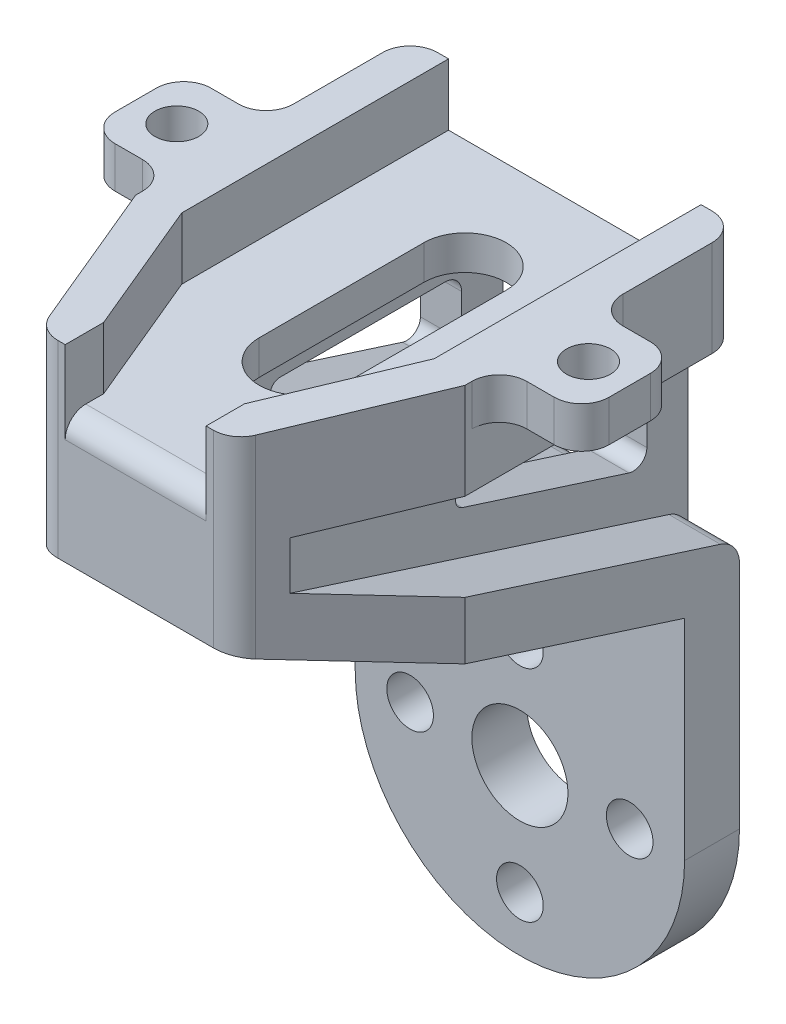
SolidWorks part; units mm, degrees
ref_plane "前视基准面" through (0, 0, 0) normal (0, 0, 1) x (1, 0, 0)
ref_plane "上视基准面" through (0, 0, 0) normal (0, 1, 0) x (1, 0, 0)
ref_plane "右视基准面" through (0, 0, 0) normal (1, 0, 0) x (0, 0, -1)
sketch "草图1" plane through (0, 0, 0) normal (0, 0, 1) x (1, 0, 0)
  line L0 (0, 148.5) -> (0, -94.9538) construction
  line L1 (105, -148.5) -> (-105, -148.5) construction
  line L2 (105, -148.5) -> (105, 148.5) construction
  line L3 (105, 148.5) -> (-105, 148.5) construction
  line L4 (-105, -148.5) -> (-105, 148.5) construction
  line L5 (105, -148.5) -> (-105, 148.5) construction
  line L6 (105, 148.5) -> (-105, -148.5) construction
  line L7 (35.8892, 121.6645) -> (-35.8892, 121.6645)
  line L8 (-35.8892, 121.6645) -> (-66.9017, 102.292)
  line L9 (-75, 40.9339) -> (-75, 31.2613)
  line L10 (-66.9017, 102.292) -> (-66.9017, 52.8701)
  line L11 (75, 40.9339) -> (75, 31.2613)
  line L12 (66.9017, 102.292) -> (66.9017, 52.8701)
  line L13 (35.8892, 121.6645) -> (66.9017, 102.292)
  line L14 (-75, 31.2613) -> (75, 31.2613)
  line L15 (-60, -148.5) -> (-60, -91.8129)
  line L16 (-75, 23.94) -> (75, 23.94)
  line L17 (-75, 23.94) -> (-75, 10.5626)
  line L18 (-38.8455, -105.5906) -> (-66.4608, -113.7617)
  line L19 (-66.4608, -113.7617) -> (-70.1743, -102.7328)
  line L20 (75, 23.94) -> (75, 10.5626)
  line L21 (66.4608, -113.7617) -> (70.1743, -102.7328)
  line L22 (38.8455, -105.5906) -> (66.4608, -113.7617)
  line L23 (-105, 93.0519) -> (105, 93.0519)
  line L24 (-105, 63.0519) -> (105, 63.0519)
  line L25 (-105, -90.0629) -> (-70.5337, -90.0629)
  line L26 (-105, -60.0629) -> (-67.4027, -60.0629)
  line L27 (60, -148.5) -> (60, 148.5)
  line L28 (-60, -58.3129) -> (-45, -58.3129)
  line L29 (-60, -61.8129) -> (-45, -61.8129)
  line L30 (-36, -58.3129) -> (-21, -58.3129)
  line L31 (-36, -61.8129) -> (-21, -61.8129)
  line L32 (-60, -88.3129) -> (-45, -88.3129)
  line L33 (-60, -91.8129) -> (-45, -91.8129)
  line L34 (-36, -88.3129) -> (-21, -88.3129)
  line L35 (-36, -91.8129) -> (-21, -91.8129)
  line L36 (-60, -58.3129) -> (-60, 148.5)
  line L37 (-19.25, -90.0629) -> (105, -90.0629)
  line L38 (-19.25, -60.0629) -> (19.25, -60.0629)
  line L39 (-60, -88.3129) -> (-60, -61.8129)
  line L40 (21, -58.3129) -> (36, -58.3129)
  line L41 (45, -58.3129) -> (60, -58.3129)
  line L42 (60, -61.8129) -> (45, -61.8129)
  line L43 (36, -61.8129) -> (21, -61.8129)
  line L44 (21, -88.3129) -> (36, -88.3129)
  line L45 (21, -91.8129) -> (36, -91.8129)
  line L46 (45, -88.3129) -> (60, -88.3129)
  line L47 (45, -91.8129) -> (60, -91.8129)
  line L48 (37.75, -60.0629) -> (43.25, -60.0629)
  line L49 (58.25, -60.0629) -> (105, -60.0629)
  line L50 (-60, 94.8019) -> (-45, 94.8019)
  line L51 (-36, 94.8019) -> (-21, 94.8019)
  line L52 (-60, 91.3019) -> (-45, 91.3019)
  line L53 (-36, 91.3019) -> (-21, 91.3019)
  line L54 (-60, 64.8019) -> (-45, 64.8019)
  line L55 (-60, 61.3019) -> (-45, 61.3019)
  line L56 (-36, 64.8019) -> (-21, 64.8019)
  line L57 (-36, 61.3019) -> (-21, 61.3019)
  line L58 (21, 94.8019) -> (36, 94.8019)
  line L59 (21, 91.3019) -> (36, 91.3019)
  line L60 (45, 94.8019) -> (60, 94.8019)
  line L61 (45, 91.3019) -> (60, 91.3019)
  line L62 (21, 61.3019) -> (36, 61.3019)
  line L63 (21, 64.8019) -> (36, 64.8019)
  line L64 (45, 61.3019) -> (60, 61.3019)
  line L65 (45, 64.8019) -> (60, 64.8019)
  line L66 (-33.1709, -104.7687) -> (33.1709, -104.7687)
  line L67 (0, -104.7687) -> (0, -148.5) construction
  arc A0 (-75, 40.9339) -> (-66.9017, 52.8701) centre (-79.7474, 52.8701) ccw
  arc A1 (75, 40.9339) -> (66.9017, 52.8701) centre (79.7474, 52.8701) cw
  arc A3 (-60, -88.3129) -> (-60, -91.8129) centre (-60, -90.0629) ccw
  arc A4 (-60, -58.3129) -> (-60, -61.8129) centre (-60, -60.0629) ccw
  circle A5 centre (-60, 63.0519) radius 1.75
  circle A6 centre (-60, 93.0519) radius 1.75
  circle A7 centre (60, 93.0519) radius 1.75
  circle A8 centre (60, 63.0519) radius 1.75
  arc A9 (60, -91.8129) -> (60, -88.3129) centre (60, -90.0629) ccw
  arc A10 (60, -61.8129) -> (60, -58.3129) centre (60, -60.0629) ccw
  arc A11 (-36, -58.3129) -> (-36, -61.8129) centre (-36, -60.0629) ccw
  arc A12 (-36, -88.3129) -> (-36, -91.8129) centre (-36, -90.0629) ccw
  arc A13 (36, -61.8129) -> (36, -58.3129) centre (36, -60.0629) ccw
  arc A14 (36, -91.8129) -> (36, -88.3129) centre (36, -90.0629) ccw
  arc A15 (-45, -61.8129) -> (-45, -58.3129) centre (-45, -60.0629) ccw
  arc A16 (-21, -61.8129) -> (-21, -58.3129) centre (-21, -60.0629) ccw
  arc A17 (-45, -91.8129) -> (-45, -88.3129) centre (-45, -90.0629) ccw
  arc A18 (-21, -91.8129) -> (-21, -88.3129) centre (-21, -90.0629) ccw
  arc A19 (45, -58.3129) -> (45, -61.8129) centre (45, -60.0629) ccw
  arc A20 (21, -58.3129) -> (21, -61.8129) centre (21, -60.0629) ccw
  arc A21 (21, -88.3129) -> (21, -91.8129) centre (21, -90.0629) ccw
  arc A22 (45, -88.3129) -> (45, -91.8129) centre (45, -90.0629) ccw
  circle A23 centre (-36, 93.0519) radius 1.75
  circle A24 centre (-36, 63.0519) radius 1.75
  circle A25 centre (36, 93.0519) radius 1.75
  circle A26 centre (36, 63.0519) radius 1.75
  circle A27 centre (-45, 93.0519) radius 1.75
  circle A28 centre (-21, 93.0519) radius 1.75
  circle A29 centre (-45, 63.0519) radius 1.75
  circle A30 centre (-21, 63.0519) radius 1.75
  circle A31 centre (21, 93.0519) radius 1.75
  circle A32 centre (21, 63.0519) radius 1.75
  circle A33 centre (45, 93.0519) radius 1.75
  circle A34 centre (45, 63.0519) radius 1.75
  arc A35 (33.1709, -104.7687) -> (38.8455, -105.5906) centre (33.1709, -124.7687) cw
  arc A36 (-33.1709, -104.7687) -> (-38.8455, -105.5906) centre (-33.1709, -124.7687) ccw
  spline S0 degree 3 poles (-75, 10.5626) (-72.6959, 1.9073) (-70.3396, -13.3728) (-67.1028, -43.6255) (-66.7657, -72.9327) (-71.8903, -95.1489) (-70.1743, -102.7328) knots 0 0 0 0 0.235247 0.406294 0.801186 1 1 1 1
  spline S1 degree 3 poles (75, 10.5626) (72.6959, 1.9073) (70.3396, -13.3728) (67.1028, -43.6255) (66.7657, -72.9327) (71.8903, -95.1489) (70.1743, -102.7328) knots 0 0 0 0 0.235247 0.406294 0.801186 1 1 1 1
  point P0 (0, 0)
  point P27 (0, 121.6645)
  point P42 (0, -94.0966)
  dimension "D1" = 60
  dimension "D4" = 20
  dimension "D5" = 24
  dimension "D7" = 24
  dimension "D9" = 15
  dimension "D10" = 15
  dimension "D13" = 24
  dimension "D17" = 15
  dimension "D2" = 30
  dimension "D3" = 30
  dimension "D6" = 24
  dimension "D8" = 24
  dimension "D11" = 15
  dimension "D12" = 15
  dimension "D14" = 24
  dimension "D15" = 24
  dimension "D16" = 24
  dimension "D18" = 15
  dimension "D19" = 15
  dimension "D20" = 15
  dimension "D21" = 15
  dimension "D22" = 15
  dimension "D23" = 15
  dimension "D24" = 15
  dimension "D25" = 15
  dimension "D26" = 15
  dimension "D27" = 15
  dimension "D28" = 15
  dimension "D29" = 3.5
  dimension "D30" = 3.5
  dimension "D31" = 3.5
extrude "凸台-拉伸1" add sketch "草图1" along normal blind 3 contours A34 L24 A26 L62 A32 A30 L57 A24 A29 L55 L36 L14 L27 L64 | A5 L24 L10 A0 L9 L14 L36 | A6 L23 L10 L24 A5 L36 | A6 L36 L8 L10 L23 | A33 L60 L27 L13 L7 L8 L36 L50 A27 L23 A23 L51 A28 A31 L58 A25 | A34 L65 L27 L61 A33 L23 A25 L59 A31 A28 L53 A23 A27 L52 L36 L54 A29 L24 A24 L56 A30 A32 L63 A26 | A7 L23 L12 L13 L27 | A8 L24 L12 L23 A7 L27 | A8 L27 L14 L11 A1 L12 L24 | A22 L46 L27 L42 A19 A13 L43 A20 A16 L31 A11 L30 L40 L41 L16 L36 L28 A15 L29 L39 L32 A17 L33 L15 L18 L22 L47 A14 L45 A21 A18 L35 A12 L34 | L17 S0 L19 L18 L15 A3 L39 A4 L36 L16 | S1 L20 L16 L27 A10 L49 | S1 L49 A10 L27 A9 L37 | S1 L37 A9 L27 L22 L21 region at (0, 106.7597, 0) region at (63.3118, 98.9762, 0) region at (-63.3118, 98.9762, 0) region at (63.5153, 78.0519, 0) region at (-63.5153, 78.0519, 0) region at (65.7633, 44.067, 0) region at (0, 78.0519, 0) region at (-65.7633, 44.067, 0) region at (0, 46.6707, 0) region at (0, -40.0712, 0) region at (65.6849, -11.6712, 0) region at (-65.3451, -38.0027, 0) region at (64.4303, -76.0355, 0) region at (65.0264, -100.7629, 0)
sketch "草图7" plane through (0, 0, 0) normal (0, 0, -1) x (-1, 0, 0)
  line L0 (0, 121.6645) -> (0, -104.7687) construction
  line L1 (-35.8892, 121.6645) -> (35.8892, 121.6645) construction
  line L2 (33.1709, -104.7687) -> (-33.1709, -104.7687) construction
  line L3 (0, 41.2613) -> (-21, 41.2613) construction
  line L4 (0, 41.2613) -> (21, 41.2613) construction
  line L5 (0, 13.94) -> (-21, 13.94) construction
  line L6 (0, 13.94) -> (21, 13.94) construction
  line L7 (75, 23.94) -> (-75, 23.94) construction
  line L8 (75, 31.2613) -> (-75, 31.2613) construction
  circle A0 centre (-21, 41.2613) radius 1.75
  circle A1 centre (21, 41.2613) radius 1.75
  circle A2 centre (-21, 13.94) radius 2.25
  circle A3 centre (21, 13.94) radius 2.25
  dimension "D1" = 10
  dimension "D2" = 10
extrude "切除-拉伸2" cut sketch "草图7" against normal through all
sketch "草图9" plane through (0, 0, 3) normal (0, 0, 1) x (1, 0, 0)
  line L0 (-70.7828, -98.747) -> (70.7828, -98.747) construction
  line L1 (0, -98.747) -> (0, -104.7687) construction
  line L2 (55, -100.497) -> (20, -100.497)
  line L3 (-55, -96.997) -> (-20, -96.997)
  line L4 (-55, -100.497) -> (-20, -100.497)
  line L5 (-33.1709, -104.7687) -> (33.1709, -104.7687) construction
  line L6 (55, -96.997) -> (20, -96.997)
  arc A0 (-55, -96.997) -> (-55, -100.497) centre (-55, -98.747) ccw
  arc A1 (-20, -100.497) -> (-20, -96.997) centre (-20, -98.747) ccw
  arc A2 (20, -100.497) -> (20, -96.997) centre (20, -98.747) cw
  arc A3 (55, -96.997) -> (55, -100.497) centre (55, -98.747) cw
  spline S0 degree 3 poles (-75, 10.5626) (-72.6959, 1.9073) (-70.3396, -13.3728) (-67.1028, -43.6255) (-66.7657, -72.9327) (-71.8903, -95.1489) (-70.1743, -102.7328) knots 0 0 0 0 0.235247 0.406294 0.801186 1 1 1 1 construction
  spline S1 degree 3 poles (75, 10.5626) (72.6959, 1.9073) (70.3396, -13.3728) (67.1028, -43.6255) (66.7657, -72.9327) (71.8903, -95.1489) (70.1743, -102.7328) knots 0 0 0 0 0.235247 0.406294 0.801186 1 1 1 1 construction
  dimension "D1" = 35
  dimension "D2" = 20
extrude "切除-拉伸4" cut sketch "草图9" against normal blind 3
sketch "草图10" plane through (0, 0, 3) normal (0, 0, 1) x (1, 0, 0)
  line L0 (-21, -60.0629) -> (-21, -90.0629) construction
  line L1 (21, -60.0629) -> (21, -90.0629) construction
  line L2 (-21, -75.0629) -> (-17.5, -75.0629) construction
  line L4 (12.5, -80.0629) -> (-12.5, -80.0629)
  line L6 (12.5, -70.0629) -> (-12.5, -70.0629)
  line L11 (17.5, -75.0629) -> (21, -75.0629) construction
  arc A0 (-12.5, -70.0629) -> (-12.5, -80.0629) centre (-12.5, -75.0629) ccw
  arc A1 (12.5, -80.0629) -> (12.5, -70.0629) centre (12.5, -75.0629) ccw
  point P11 (0, -75.0629)
extrude "切除-拉伸5" cut sketch "草图10" against normal blind 3
sketch "草图11" plane through (0, 0, 3) normal (0, 0, 1) x (1, 0, 0)
  line L0 (-21, 93.0519) -> (-21, 63.0519) construction
  line L1 (21, 93.0519) -> (21, 63.0519) construction
  line L2 (-21, 78.0519) -> (-20, 78.0519) construction
  line L4 (15, 73.0519) -> (-15, 73.0519)
  line L6 (15, 83.0519) -> (-15, 83.0519)
  line L10 (20, 78.0519) -> (21, 78.0519) construction
  arc A0 (-15, 83.0519) -> (-15, 73.0519) centre (-15, 78.0519) ccw
  arc A1 (15, 73.0519) -> (15, 83.0519) centre (15, 78.0519) ccw
  point P10 (0, 78.0519)
  dimension "D1" = 30
extrude "切除-拉伸8" cut sketch "草图11" against normal blind 3
sketch "草图12" plane through (0, 0, 3) normal (0, 0, 1) x (1, 0, 0)
  line L0 (0, 121.6645) -> (0, 83.0519) construction
  line L1 (35.8892, 121.6645) -> (-35.8892, 121.6645) construction
  line L2 (15, 83.0519) -> (-15, 83.0519) construction
  circle A0 centre (0, 106.3718) radius 11 construction
  circle A1 centre (0, 106.3718) radius 8 construction
  circle A2 centre (0, 114.3718) radius 1.7
  circle A3 centre (0, 98.3718) radius 1.7
  circle A4 centre (8, 106.3718) radius 1.7
  circle A5 centre (-8, 106.3718) radius 1.7
extrude "切除-拉伸9" cut sketch "草图12" against normal blind 3
sketch "草图13" plane through (0, 0, 3) normal (0, 0, 1) x (1, 0, 0)
  line L0 (0, -104.7687) -> (0, -80.0629) construction
  line L1 (-33.1709, -104.7687) -> (33.1709, -104.7687) construction
  line L2 (-12.5, -80.0629) -> (12.5, -80.0629) construction
  circle A0 centre (0, -92.4158) radius 8 construction
  circle A1 centre (0, -84.4158) radius 1.7
  circle A2 centre (8, -92.4158) radius 1.7
  circle A3 centre (0, -100.4158) radius 1.7
  circle A4 centre (-8, -92.4158) radius 1.7
extrude "切除-拉伸11" cut sketch "草图13" against normal blind 3
sketch "草图14" plane through (0, 0, 3) normal (0, 0, 1) x (1, 0, 0)
  line L0 (0, 23.94) -> (0, -104.7687) construction
  line L1 (-55.4755, 8.9197) -> (-55.4755, -46.0803)
  line L2 (-58.9755, 8.9197) -> (-58.9755, -46.0803)
  line L3 (-75, 23.94) -> (75, 23.94) construction
  line L4 (-33.1709, -104.7687) -> (33.1709, -104.7687) construction
  line L5 (58.9755, 8.9197) -> (58.9755, -46.0803)
  line L6 (55.4755, 8.9197) -> (55.4755, -46.0803)
  arc A0 (-55.4755, 8.9197) -> (-58.9755, 8.9197) centre (-57.2255, 8.9197) ccw
  arc A1 (-58.9755, -46.0803) -> (-55.4755, -46.0803) centre (-57.2255, -46.0803) ccw
  arc A2 (58.9755, -46.0803) -> (55.4755, -46.0803) centre (57.2255, -46.0803) cw
  arc A3 (55.4755, 8.9197) -> (58.9755, 8.9197) centre (57.2255, 8.9197) cw
extrude "切除-拉伸12" cut sketch "草图14" against normal through all
fillet "圆角1" radius 2 2 edges at (75, 31.2613, 1.5) (-75, 31.2613, 1.5)
fillet "圆角2" radius 2 2 edges at (-75, 23.94, 1.5) (75, 23.94, 1.5)
sketch "草图15" plane through (0, 0, 0) normal (0, 0, -1) x (-1, 0, 0)
  line L0 (0, 121.6645) -> (0, 31.2613) construction
  line L1 (-35.8892, 121.6645) -> (35.8892, 121.6645) construction
  line L2 (73, 31.2613) -> (-73, 31.2613) construction
  line L3 (-27.5188, 121.6645) -> (-63.6963, 99.0657) construction
  line L4 (-35.8892, 121.6645) -> (-66.9017, 102.292) construction
  line L5 (-61.1842, 102.4035) -> (-34.7748, 118.9006)
  line L6 (-59.5948, 99.8591) -> (-33.1854, 116.3562)
  line L7 (27.5188, 121.6645) -> (63.6963, 99.0657) construction
  line L8 (59.5948, 99.8591) -> (33.1854, 116.3562)
  line L9 (61.1842, 102.4035) -> (34.7748, 118.9006)
  arc A0 (-61.1842, 102.4035) -> (-59.5948, 99.8591) centre (-60.3895, 101.1313) ccw
  arc A1 (-33.1854, 116.3562) -> (-34.7748, 118.9006) centre (-33.9801, 117.6284) ccw
  arc A2 (33.1854, 116.3562) -> (34.7748, 118.9006) centre (33.9801, 117.6284) cw
  arc A3 (61.1842, 102.4035) -> (59.5948, 99.8591) centre (60.3895, 101.1313) cw
extrude "切除-拉伸13" cut sketch "草图15" against normal through all
sketch "草图16" plane through (0, 0, 0) normal (0, 0, -1) x (-1, 0, 0)
  line L0 (0, 121.6645) -> (0, 31.2613) construction
  line L1 (-35.8892, 121.6645) -> (35.8892, 121.6645) construction
  line L2 (73, 31.2613) -> (-73, 31.2613) construction
  line L3 (-21, 41.2613) -> (-66.71, 41.2613) construction
  line L4 (-62, 43.0113) -> (-32, 43.0113)
  line L5 (-62, 39.5113) -> (-32, 39.5113)
  line L6 (21, 41.2613) -> (66.71, 41.2613) construction
  line L7 (62, 39.5113) -> (32, 39.5113)
  line L8 (62, 43.0113) -> (32, 43.0113)
  line L9 (-75, 40.9339) -> (-75, 33.2613) construction
  arc A0 (-62, 43.0113) -> (-62, 39.5113) centre (-62, 41.2613) ccw
  arc A1 (-32, 39.5113) -> (-32, 43.0113) centre (-32, 41.2613) ccw
  arc A2 (32, 39.5113) -> (32, 43.0113) centre (32, 41.2613) cw
  arc A3 (62, 43.0113) -> (62, 39.5113) centre (62, 41.2613) cw
  dimension "D2" = 13
sketch "草图17" plane through (0, 0, 0) normal (0, 0, -1) x (-1, 0, 0)
  text T0 "Y" font "黑体" height in points 72
extrude "切除-拉伸15" cut sketch "草图17" against normal through all
sketch "草图18" plane through (0, 0, 0) normal (0, 0, -1) x (-1, 0, 0)
  text T0 "H" font "黑体" height in points 72
extrude "切除-拉伸16" cut sketch "草图18" against normal through all
sketch "草图20" plane through (0, 0, 0) normal (0, 0, -1) x (-1, 0, 0)
  line L0 (-66.9017, 102.292) -> (-66.9017, 52.8701) construction
  line L1 (-66.9017, 95.8596) -> (66.9017, 95.8596)
  line L2 (-66.9017, 95.8596) -> (-66.9017, 52.8701)
  line L3 (-66.9017, 52.8701) -> (66.9017, 52.8701)
  line L4 (66.9017, 95.8596) -> (66.9017, 52.8701)
extrude "凸台-拉伸2" add sketch "草图20" against normal blind 3
sketch "草图21" plane through (0, 0, 0) normal (0, 0, -1) x (-1, 0, 0)
  line L1 (-64.7663, -56.4228) -> (64.4409, -56.4228)
  line L2 (-64.7663, -56.4228) -> (-64.7663, -95.2117)
  line L3 (-64.7663, -95.2117) -> (64.4409, -95.2117)
  line L4 (64.4409, -56.4228) -> (64.4409, -95.2117)
extrude "凸台-拉伸3" add sketch "草图21" against normal blind 3
sketch "草图22" plane through (0, 0, 0) normal (0, 0, -1) x (-1, 0, 0)
  line L1 (-46.7188, -3.1128) -> (-25.8503, -3.1128)
  line L2 (-46.7188, -3.1128) -> (-46.7188, -34.3233)
  line L3 (-46.7188, -34.3233) -> (-25.8503, -34.3233)
  line L4 (-25.8503, -3.1128) -> (-25.8503, -34.3233)
  line L5 (28.8143, -3.1128) -> (49.8675, -3.1128)
  line L6 (28.8143, -3.1128) -> (28.8143, -33.2152)
  line L7 (28.8143, -33.2152) -> (49.8675, -33.2152)
  line L8 (49.8675, -3.1128) -> (49.8675, -33.2152)
extrude "凸台-拉伸4" add sketch "草图22" against normal blind 3
sketch "草图24" plane through (0, 0, 0) normal (0, 0, -1) x (-1, 0, 0)
  line L1 (-64.9961, 44.3276) -> (-28.6954, 44.3276)
  line L2 (-64.9961, 44.3276) -> (-64.9961, 38.3743)
  line L3 (-64.9961, 38.3743) -> (-28.6954, 38.3743)
  line L4 (-28.6954, 44.3276) -> (-28.6954, 38.3743)
  line L5 (29.2405, 44.3276) -> (65.8315, 44.3276)
  line L6 (29.2405, 44.3276) -> (29.2405, 38.3743)
  line L7 (29.2405, 38.3743) -> (65.8315, 38.3743)
  line L8 (65.8315, 44.3276) -> (65.8315, 38.3743)
extrude "凸台-拉伸5" add sketch "草图24" against normal blind 3
sketch "草图25" plane through (0, 0, 0) normal (0, 0, -1) x (-1, 0, 0)
  line L0 (-32.6582, 113.0113) -> (-14.6582, 113.0113)
  line L1 (-32.6582, 109.5113) -> (-14.6582, 109.5113)
  line L2 (-21, 41.2613) -> (21, 41.2613)
  line L3 (-0.3165, 111.2613) -> (0, 41.2613) construction
  line L4 (14.3418, 113.0113) -> (32.3418, 113.0113)
  line L5 (32.3418, 41.2613) -> (-32.6582, 41.2613)
  line L6 (32.3418, 41.2613) -> (32.3418, 111.2613)
  line L8 (-32.6582, 41.2613) -> (-32.6582, 111.2613)
  line L9 (32.3418, 41.2613) -> (-32.6582, 111.2613) construction
  line L10 (30.7168, 109.5113) -> (-32.6582, 41.2613) construction
  line L11 (14.3418, 109.5113) -> (32.3418, 109.5113)
  line L12 (32.3418, 76.2613) -> (-32.6582, 76.2613) construction
  line L13 (12.5918, 111.2613) -> (-12.9082, 111.2613)
  line L14 (12.5918, 41.2613) -> (-12.9082, 41.2613)
  line L15 (14.3418, 43.0113) -> (32.3418, 43.0113)
  line L16 (14.3418, 39.5113) -> (32.3418, 39.5113)
  line L17 (-32.6582, 43.0113) -> (-14.6582, 43.0113)
  line L18 (-32.6582, 39.5113) -> (-14.6582, 39.5113)
  circle A0 centre (-32.6582, 111.2613) radius 1.75
  arc A1 (32.3418, 109.5113) -> (32.3418, 113.0113) centre (32.3418, 111.2613) ccw
  arc A2 (-14.6582, 109.5113) -> (-14.6582, 113.0113) centre (-14.6582, 111.2613) ccw
  arc A3 (14.3418, 113.0113) -> (14.3418, 109.5113) centre (14.3418, 111.2613) ccw
  arc A4 (14.3418, 39.5113) -> (14.3418, 43.0113) centre (14.3418, 41.2613) cw
  arc A5 (-14.6582, 43.0113) -> (-14.6582, 39.5113) centre (-14.6582, 41.2613) cw
  arc A6 (32.3418, 43.0113) -> (32.3418, 39.5113) centre (32.3418, 41.2613) cw
  circle A7 centre (-32.6582, 41.2613) radius 1.75
  point P9 (-0.1582, 76.2613)
  circle M6 centre (-21, 41.2613) radius 1.75
  circle M7 centre (21, 41.2613) radius 1.75
  dimension "D1" = 18
  dimension "D2" = 18
extrude "切除-拉伸17" cut sketch "草图25" against normal through all contours A0 | A2 L0 A0 L1 | L4 A3 L11 A1 | A7 L8 L5 | A7 L5 L8 | L17 A7 L5 M6 | L5 A7 L18 M6 | A5 L17 L2 M6 | A5 L2 L18 M6 | L17 L5 L2 M6 | L18 L2 L5 M6 | A4 L2 L15 M7 | A4 L16 L2 M7 | L16 L5 L2 M7 | L15 L2 L5 M7 | L15 L5 L6 M7 | A6 L6 L5 L16 M7 region at (22.2838, 111.2613, 0) region at (31.4558, 112.4638, 0) region at (31.9155, 42.0041, 0) region at (26.8291, 42.1772, 0) region at (32.9058, 41.0138, 0) region at (-23.3418, 111.2613, 0) region at (16.4547, 42.1363, 0) region at (21, 42.0041, 0) region at (26.8291, 40.3455, 0) region at (21, 40.5186, 0) region at (16.4547, 40.3863, 0) region at (-28.59, 40.5612, 0) region at (-27.3505, 42.1546, 0) region at (-16.2964, 42.1363, 0) region at (-16.2964, 40.3863, 0) region at (-21, 42.0041, 0) region at (-21, 40.5186, 0)
extrude "切除-拉伸19" cut sketch "草图16" against normal through all
sketch "草图26" plane through (0, 0, 0) normal (0, 0, -1) x (-1, 0, 0)
  line L0 (0, 121.6645) -> (0, -104.7687) construction
  line L1 (-35.8892, 121.6645) -> (35.8892, 121.6645) construction
  line L2 (33.1709, -104.7687) -> (-33.1709, -104.7687) construction
  line L4 (15, 71.877) -> (-15, 71.877)
  line L6 (15, 81.877) -> (-15, 81.877)
  arc A0 (-15, 81.877) -> (-15, 71.877) centre (-15, 76.877) ccw
  arc A1 (15, 71.877) -> (15, 81.877) centre (15, 76.877) ccw
  point P6 (0, 76.877)
extrude "切除-拉伸20" cut sketch "草图26" against normal through all
sketch "草图27" plane through (0, 0, 0) normal (0, 0, -1) x (-1, 0, 0)
  line L0 (0, 23.94) -> (0, -104.7687) construction
  line L1 (73, 23.94) -> (-73, 23.94) construction
  line L2 (33.1709, -104.7687) -> (-33.1709, -104.7687) construction
  line L3 (-42.5, -15.81) -> (-10, -15.81)
  line L4 (42.5, -17.56) -> (-42.5, -17.56)
  line L5 (42.5, -17.56) -> (42.5, 5.44)
  line L6 (42.5, 5.44) -> (-42.5, 5.44)
  line L7 (-42.5, -17.56) -> (-42.5, 5.44)
  line L8 (42.5, -17.56) -> (-42.5, 5.44) construction
  line L9 (42.5, 5.44) -> (-42.5, -17.56) construction
  line L10 (-42.5, -19.31) -> (-10, -19.31)
  line L11 (-42.5, 7.19) -> (-10, 7.19)
  line L12 (-42.5, 3.69) -> (-10, 3.69)
  line L13 (10, 7.19) -> (42.5, 7.19)
  line L14 (10, 3.69) -> (42.5, 3.69)
  line L15 (10, -15.81) -> (42.5, -15.81)
  line L16 (10, -19.31) -> (42.5, -19.31)
  circle A0 centre (-42.5, 5.44) radius 1.75
  circle A1 centre (-42.5, -17.56) radius 1.75
  circle A2 centre (42.5, 5.44) radius 1.75
  circle A3 centre (42.5, -17.56) radius 1.75
  circle A4 centre (-10, 5.44) radius 1.75
  circle A5 centre (-10, -17.56) radius 1.75
  circle A6 centre (10, -17.56) radius 1.75
  circle A7 centre (10, 5.44) radius 1.75
  point P6 (0, -6.06)
  dimension "D4" = 10
  dimension "D5" = 10
  dimension "D1" = 30
  dimension "D2" = 85
  dimension "D3" = 23
extrude "切除-拉伸21" cut sketch "草图27" against normal through all contours L6 A0 L7 | L7 A0 L6 | A4 L11 A0 L6 | A4 L6 A0 L12 | L6 A4 | L6 A4 | A7 L6 | A7 L6 | L6 A7 L14 A2 | L13 A7 L6 A2 | A2 L6 L5 | L6 A2 L5 | L7 A1 L4 | L4 A1 L7 | A5 L3 A1 L4 | A5 L4 A1 L10 | L4 A5 | L4 A5 | A6 L4 | A6 L4 | L4 A6 L16 A3 | L15 A6 L4 A3 | L4 A3 L5 | L5 A3 L4 region at (41.7573, -16.8172, 0) region at (26.25, -16.6727, 0) region at (42.7476, -17.8075, 0) region at (10, -16.8172, 0) region at (42.7476, 5.6876, 0) region at (26.25, 4.5528, 0) region at (41.7573, 4.6973, 0) region at (26.25, -18.4472, 0) region at (10, -18.3027, 0) region at (10, 4.6973, 0) region at (26.25, 6.3273, 0) region at (-10, -16.8172, 0) region at (-10, -18.3027, 0) region at (10, 6.1828, 0) region at (-26.25, -16.6727, 0) region at (-26.25, -18.4472, 0) region at (-10, 6.1828, 0) region at (-10, 4.6973, 0) region at (-41.7573, -16.8172, 0) region at (-42.7476, -17.8075, 0) region at (-26.25, 6.3273, 0) region at (-26.25, 4.5528, 0) region at (-41.7573, 4.6973, 0) region at (-42.7476, 5.6876, 0)
sketch "草图28" plane through (0, 0, 0) normal (0, 0, -1) x (-1, 0, 0)
  line L0 (0, 23.94) -> (0, -104.7687) construction
  line L1 (73, 23.94) -> (-73, 23.94) construction
  line L2 (33.1709, -104.7687) -> (-33.1709, -104.7687) construction
  arc A0 (0, -48.8123) -> (-10.2848, -54.2659) centre (-5.1424, -51.5391) ccw
  arc A1 (-10.2848, -54.2659) -> (0, -63.7557) centre (7.9187, -44.8556) ccw
  arc A2 (10.2848, -54.2659) -> (0, -63.7557) centre (-7.9187, -44.8556) cw
  arc A3 (0, -48.8123) -> (10.2848, -54.2659) centre (5.1424, -51.5391) cw
extrude "切除-拉伸22" cut sketch "草图28" against normal through all
sketch "草图29" plane through (0, 0, 0) normal (0, 0, -1) x (-1, 0, 0)
  line L0 (0, 23.94) -> (0, -104.7687) construction
  line L1 (73, 23.94) -> (-73, 23.94) construction
  line L2 (33.1709, -104.7687) -> (-33.1709, -104.7687) construction
  arc A0 (-21.3687, -73.4908) -> (21.3687, -73.4908) centre (0, -58.7579) ccw
  arc A1 (-24.1996, -75.4426) -> (24.1996, -75.4426) centre (0, -58.7579) ccw
  arc A2 (-21.3687, -73.4908) -> (-24.1996, -75.4426) centre (-22.7842, -74.4667) ccw
  arc A3 (24.1996, -75.4426) -> (21.3687, -73.4908) centre (22.7842, -74.4667) ccw
extrude "切除-拉伸23" cut sketch "草图29" against normal blind 3
ref_plane "基准面1" through (0, 0, -10) normal (0, 0, -1) x (-1, 0, 0)
sketch "草图30" plane through (0, 0, -10) normal (0, 0, -1) x (-1, 0, 0)
  line L0 (-8, 106.3718) -> (8, 106.3718) construction
  line L1 (-12, 106.3718) -> (-12, 141.6645)
  line L2 (12, 106.3718) -> (12, 141.6645)
  line L3 (-35.8892, 121.6645) -> (35.8892, 121.6645) construction
  line L4 (-12, 141.6645) -> (12, 141.6645)
  circle A0 centre (8, 106.3718) radius 1.7 construction
  circle A1 centre (0, 98.3718) radius 1.7 construction
  circle A2 centre (-8, 106.3718) radius 1.7 construction
  circle A3 centre (0, 114.3718) radius 1.7 construction
  circle A4 centre (8, 106.3718) radius 1.7
  circle A5 centre (0, 98.3718) radius 1.7
  circle A6 centre (-8, 106.3718) radius 1.7
  circle A7 centre (0, 114.3718) radius 1.7
  arc A8 (-12, 106.3718) -> (12, 106.3718) centre (0, 106.3718) ccw
  circle A9 centre (0, 106.3718) radius 3.5
  dimension "D1" = 20
  dimension "D2" = 20
extrude "凸台-拉伸6" add sketch "草图30" along normal blind 4 separate body
sketch "草图31" plane through (-12, 0, 0) normal (-1, 0, 0) x (0, 0, 1)
  line L0 (0, 121.6645) -> (-10, 121.6645) construction
  line L2 (-10, 121.6645) -> (-10, 125.8643) construction
  line L4 (-10, 121.6645) -> (15, 129.6645)
  line L5 (-10, 125.8643) -> (15, 133.8643)
  line L6 (15, 133.8643) -> (15, 139.3643)
  line L7 (18, 130.6245) -> (18, 139.3643)
  line L8 (15, 129.6645) -> (18, 130.6245)
  line L9 (15, 139.3643) -> (18, 139.3643)
  line L10 (-10, 121.6645) -> (-10, 125.8643)
  dimension "D1" = 25
  dimension "D2" = 5.5
  dimension "D3" = 4
  dimension "D4" = 3
extrude "凸台-拉伸7" add sketch "草图31" against normal up to surface (24 mm away) up to face at (12, 124.0182, -12)
sketch "草图32" plane through (-12, 0, 0) normal (-1, 0, 0) x (0, 0, 1)
  line L0 (15, 133.8643) -> (-10, 125.8643) construction
  line L1 (15, 133.8643) -> (-10, 125.8643)
  line L2 (-10, 125.8643) -> (-14, 124.5843)
  line L5 (-10, 141.6645) -> (-10, 125.8643)
  line L6 (-14, 106.3718) -> (-14, 141.6645) construction
  line L7 (-14, 141.6645) -> (-10, 141.6645) construction
  line L8 (-14, 141.6645) -> (-10, 141.6645)
  line L9 (-14, 106.3718) -> (-14, 141.6645)
  line M12 (-10, 125.8643) -> (-10, 141.6645)
  line M13 (-10, 141.6645) -> (-14, 141.6645)
  line M14 (-14, 141.6645) -> (-14, 106.3718)
extrude "切除-拉伸26" cut sketch "草图32" against normal blind 31.5 contours L2 M12 M13 M14 region at (-12, 133.4403, -12.026)
sketch "草图34" plane through (0, 139.3643, 0) normal (0, 1, 0) x (1, 0, 0)
  line L0 (0, -18.0398) -> (0, 14) construction
  line L1 (12, 14) -> (-12, 14) construction
  line L2 (-12, -6) -> (-7, -18)
  line L3 (-12, 14) -> (12, 14)
  line L4 (-12, 14) -> (-12, -6)
  line L5 (-7, -18) -> (7, -18)
  line L6 (12, 14) -> (12, -6)
  line L7 (12, -6) -> (7, -18)
extrude "凸台-拉伸8" add sketch "草图34" along normal blind 10
ref_plane "基准面2" through (0, 137.3643, 0) normal (0, -1, 0) x (-1, 0, 0)
sketch "草图36" plane through (0, 137.3643, 0) normal (0, -1, 0) x (-1, 0, 0)
  line L6 (-12, -6) -> (-8.25, -15)
  line L7 (-8.25, -15) -> (8.25, -15)
  line L8 (8.25, -15) -> (12, -6)
  line L9 (12, -6) -> (12, 14)
  line L10 (12, 14) -> (-12, 14)
  line L11 (-12, 14) -> (-12, -6)
  line L12 (-12, -6) -> (-8.25, -15)
  line L13 (-8.25, -15) -> (8.25, -15)
  line L14 (8.25, -15) -> (12, -6)
  line L15 (12, -6) -> (12, 14)
  line L16 (12, 14) -> (-12, 14)
  line L17 (-12, 14) -> (-12, -6)
  dimension "D1" = 0
extrude "凸台-拉伸9" add sketch "草图36" against normal blind 1
sketch "草图37" plane through (0, 149.3643, 0) normal (0, 1, 0) x (1, 0, 0)
  line L6 (-12, 14) -> (-12, -6)
  line L7 (-12, -6) -> (-7, -18)
  line L8 (-7, -18) -> (7, -18)
  line L9 (7, -18) -> (12, -6)
  line L10 (12, -6) -> (12, 14)
  line L11 (12, 14) -> (-12, 14)
  line L12 (-12, 14) -> (-12, -6)
  line L13 (-12, -6) -> (-7, -18)
  line L14 (-7, -18) -> (7, -18)
  line L15 (7, -18) -> (12, -6)
  line L16 (12, -6) -> (12, 14)
  line L17 (12, 14) -> (-12, 14)
  dimension "D1" = 0
extrude "切除-拉伸27" cut sketch "草图37" against normal up to surface (10 mm away) up to face at (0, 139.3643, 2.3333)
sketch "草图38" plane through (-12, 0, 0) normal (-1, 0, 0) x (0, 0, 1)
  line L1 (15, 138.3643) -> (18, 138.3643)
  line L2 (15, 138.3643) -> (15, 139.3643)
  line L3 (15, 139.3643) -> (18, 139.3643)
  line L4 (18, 138.3643) -> (18, 139.3643)
extrude "切除-拉伸28" cut sketch "草图38" against normal through all
sketch "草图39" plane through (0, 138.3643, 0) normal (0, 1, 0) x (1, 0, 0)
  line L0 (12, -6) -> (8.25, -15) construction
  line L1 (-8.25, -15) -> (-12, -6) construction
  line L2 (12, -6) -> (8.25, -15)
  line L3 (-8.25, -15) -> (-12, -6)
  line L4 (-8.25, -15) -> (-7, -18)
  line L5 (8.25, -15) -> (7, -18)
  line L6 (-12, -6) -> (-12, -18)
  line L7 (-12, -18) -> (-7, -18)
  line L8 (12, -18) -> (12, -6)
  line L9 (7, -18) -> (12, -18)
extrude "切除-拉伸29" cut sketch "草图39" against normal blind 21
sketch "草图41" plane through (0, 138.3643, 0) normal (0, 1, 0) x (1, 0, 0)
  line L6 (-7, -18) -> (7, -18)
  line L7 (7, -18) -> (12, -6)
  line L8 (12, -6) -> (12, 14)
  line L9 (12, 14) -> (-12, 14)
  line L10 (-12, 14) -> (-12, -6)
  line L11 (-12, -6) -> (-7, -18)
  line L12 (-7, -18) -> (7, -18)
  line L13 (7, -18) -> (12, -6)
  line L14 (12, -6) -> (12, 14)
  line L15 (12, 14) -> (-12, 14)
  line L16 (-12, 14) -> (-12, -6)
  line L17 (-12, -6) -> (-7, -18)
  dimension "D1" = 0
extrude "凸台-拉伸11" add sketch "草图41" along normal blind 7
sketch "草图42" plane through (0, 145.3643, 0) normal (0, 1, 0) x (1, 0, 0)
  line L0 (0, 14) -> (0, -18) construction
  line L1 (12, 14) -> (-12, 14) construction
  line L2 (-7, -18) -> (7, -18) construction
  line L3 (-9.2, 11.2) -> (-9.2, -5.44)
  line L4 (-9.2, -5.44) -> (-5.1333, -15.2)
  line L6 (5.1333, -15.2) -> (9.2, -5.44)
  line L7 (9.2, -5.44) -> (9.2, 11.2)
  line L9 (-12, -6) -> (-7, -18)
  line L10 (-7, -18) -> (7, -18)
  line L11 (7, -18) -> (12, -6)
  line L12 (12, -6) -> (12, 14)
  line L13 (12, 14) -> (-12, 14)
  line L14 (-12, 14) -> (-12, -6)
  line L19 (9.2, 14) -> (-9.2, 14)
  line L21 (-9.2, 11.2) -> (-9.2, 14)
  line L22 (9.2, 11.2) -> (9.2, 14)
  line L23 (9.2, 11.2) -> (-9.2, 11.2) construction
  line L24 (-9.2, 14) -> (9.2, 14)
  line L25 (-7, -18) -> (7, -18) construction
  line L26 (12, 14) -> (-12, 14) construction
  line L27 (12, -6) -> (12, 14) construction
  line L28 (-12, 14) -> (-12, -6) construction
  line L29 (-12, -6) -> (-7, -18) construction
  line L30 (7, -18) -> (12, -6) construction
  line L31 (-5.1333, -15.2) -> (5.1333, -15.2) construction
  line L32 (5.1333, -18.7961) -> (-5.1333, -18.7961)
  line L33 (5.1333, -18.7961) -> (5.1333, -15.2)
  line L35 (-5.1333, -18.7961) -> (-5.1333, -15.2)
  point P18 (0, -16.998)
  line M21 (-7, -18) -> (7, -18)
  line M24 (12, 14) -> (-12, 14)
  dimension "D1" = 0
  dimension "D2" = 2.8
extrude "切除-拉伸30" cut sketch "草图42" against normal blind 5.5 contours L35 L33 L6 L7 L22 L21 L3 L4 M21 M24 region at (0, 145.3643, 0.6182)
ref_plane "基准面3" through (-8.25, 0, 0) normal (-1, 0, 0) x (0, 0, 1)
sketch "草图43" plane through (-8.25, 0, 0) normal (-1, 0, 0) x (0, 0, 1)
  line L0 (15, 137.3643) -> (-14, 137.3643)
  line L1 (-14, 137.3643) -> (-14, 124.5843)
  line L2 (-14, 124.5843) -> (15, 133.8643)
  line L3 (15, 133.8643) -> (15, 137.3643)
extrude "凸台-拉伸12" add sketch "草图43" against normal blind 3
mirror "镜向1" about plane through (0, 0, 0) normal (1, 0, 0) of "凸台-拉伸12"
sketch "草图44" plane through (-8.25, 0, 0) normal (-1, 0, 0) x (0, 0, 1)
  line L0 (-11, 128.6942) -> (6.7192, 134.3643)
  line L1 (6.7192, 134.3643) -> (6.7192, 134.3643)
  line L2 (-11, 134.3643) -> (6.7192, 134.3643)
  line L3 (-11, 134.3643) -> (-11, 128.6942)
  line L4 (15, 133.8643) -> (15, 137.3643)
  line L5 (15, 137.3643) -> (-14, 137.3643)
  line L6 (-14, 137.3643) -> (-14, 124.5843)
  line L7 (-14, 124.5843) -> (15, 133.8643)
  line L8 (15, 133.8643) -> (15, 137.3643)
  line L10 (-14, 137.3643) -> (-14, 124.5843)
  line L11 (-14, 124.5843) -> (15, 133.8643)
  line L12 (-11, 128.6942) -> (6.7192, 134.3643) construction
  line L13 (6.7192, 134.3643) -> (-11, 134.3643) construction
  line L14 (15, 137.3643) -> (-14, 137.3643) construction
  point P9 (6.7192, 134.3643)
  dimension "D1" = 0
  dimension "D2" = 3
extrude "切除-拉伸31" cut sketch "草图44" against normal blind 23 contours L2 L3 L0 region at (-8.25, 132.4743, -5.0936)
fillet "圆角4" radius 0.7 2 edges at (6.75, 134.3643, 6.7192) (-6.75, 134.3643, 6.7192)
fillet "圆角5" radius 1 2 edges at (6.75, 128.6942, -11) (-6.75, 128.6942, -11)
fillet "圆角6" radius 1.2 2 edges at (6.75, 134.3643, -11) (-6.75, 134.3643, -11)
sketch "草图45" plane through (0, 139.8643, 0) normal (0, 1, 0) x (1, 0, 0)
  line L0 (0, 14) -> (0, 9) construction
  line L1 (9.2, 14) -> (-9.2, 14) construction
  line L2 (-5.1333, -18) -> (5.1333, -18) construction
  line L9 (3, -6) -> (3, 6)
  line L11 (-3, -6) -> (-3, 6)
  line L14 (0, -9) -> (0, -18) construction
  arc A1 (-3, -6) -> (3, -6) centre (0, -6) ccw
  arc A2 (3, 6) -> (-3, 6) centre (0, 6) ccw
  point P6 (0, 0)
extrude "切除-拉伸32" cut sketch "草图45" against normal blind 3
sketch "草图47" plane through (0, 0, -14) normal (0, 0, -1) x (-1, 0, 0)
  line L0 (-12, 145.3643) -> (-12, 137.3643) construction
  line L1 (12, 145.3643) -> (-12, 145.3643)
  line L2 (12, 145.3643) -> (12, 144.3643)
  line L3 (12, 144.3643) -> (-12, 144.3643)
  line L4 (-12, 145.3643) -> (-12, 144.3643)
extrude "切除-拉伸33" cut sketch "草图47" against normal through all
ref_plane "基准面4" through (0, 148.3643, 0) normal (0, 1, 0) x (1, 0, 0)
sketch "草图48" plane through (0, 144.3643, 0) normal (0, 1, 0) x (1, 0, 0)
  line L0 (-18, 0) -> (-12, 0) construction
  line L1 (-12, -6) -> (-12, 14) construction
  line L2 (0, 14) -> (0, -18) construction
  line L4 (-12, 3.5) -> (-12, -3.5)
  line L5 (-12, -3.5) -> (-18, -3.5)
  line L7 (-12, 3.5) -> (-18, 3.5)
  line L8 (-18, -3.5) -> (-18, 3.5)
  line L9 (-12, 0) -> (-18, 3.5) construction
  line L10 (-12, 0) -> (-18, -3.5) construction
  line L11 (9.2, 14) -> (-9.2, 14) construction
  line L12 (-5.1333, -18) -> (5.1333, -18) construction
  line L13 (12, 0) -> (18, -3.5) construction
  line L14 (12, 0) -> (18, 3.5) construction
  line L15 (18, 0) -> (12, 0) construction
  line L16 (18, -3.5) -> (18, 3.5)
  line L17 (12, 3.5) -> (18, 3.5)
  line L18 (12, -3.5) -> (18, -3.5)
  line L19 (12, 3.5) -> (12, -3.5)
  circle A0 centre (-15, 0) radius 1.6
  circle A1 centre (15, 0) radius 1.6
extrude "凸台-拉伸13" add sketch "草图48" against normal blind 3
fillet "圆角7" radius 2 8 edges at (12, 142.8643, 3.5) (18, 142.8643, 3.5) (18, 142.8643, -3.5) (12, 142.8643, -3.5) (-12, 142.8643, 3.5) (-18, 142.8643, 3.5) (-18, 142.8643, -3.5) (-12, 142.8643, -3.5)
mirror "镜向2" about plane through (0, 148.3643, 0) normal (0, 1, 0) of bodies 153
sketch "草图49" plane through (-12, 0, 0) normal (-1, 0, 0) x (0, 0, 1)
  line L1 (-14, 159.3643) -> (26.5189, 159.3643)
  line L2 (-14, 159.3643) -> (-14, 205.25)
  line L3 (-14, 205.25) -> (26.5189, 205.25)
  line L4 (26.5189, 159.3643) -> (26.5189, 205.25)
extrude "切除-拉伸34" cut sketch "草图49" against normal blind 33
fillet "圆角8" radius 2 4 edges at (7, 155.8643, 18) (-7, 155.8643, 18) (12, 155.8643, -14) (-12, 155.8643, -14)
fillet "圆角9" radius 2 2 edges at (7, 137.4944, 18) (-7, 137.4944, 18)
fillet "圆角10" radius 2 2 edges at (12, 140.8643, -14) (-12, 140.8643, -14)
sketch "草图50" plane through (0, 0, 0) normal (0, 0, -1) x (-1, 0, 0)
  line L1 (-85.8546, 122.695) -> (84.3906, 122.695)
  line L2 (-85.8546, 122.695) -> (-85.8546, -133.3077)
  line L3 (-85.8546, -133.3077) -> (84.3906, -133.3077)
  line L4 (84.3906, 122.695) -> (84.3906, -133.3077)
extrude "切除-拉伸35" cut sketch "草图50" against normal blind 33
fillet "圆角11" radius 2 3 edges at (10.125, 124.5843, -14) (0, 124.5843, -14) (-10.125, 124.5843, -14)
fillet "圆角12" radius 1.5 1 edges at (0, 156.8643, 18)
fillet "圆角13" radius 1.5 1 edges at (0, 139.8643, 18)
sketch "草图51" plane through (0, 0, -14) normal (0, 0, -1) x (-1, 0, 0)
  line L1 (20.0257, 150.59) -> (-19.8364, 150.59)
  line L2 (20.0257, 150.59) -> (20.0257, 163.533)
  line L3 (20.0257, 163.533) -> (-19.8364, 163.533)
  line L4 (-19.8364, 150.59) -> (-19.8364, 163.533)
extrude "切除-拉伸36" cut sketch "草图51" against normal blind 40
